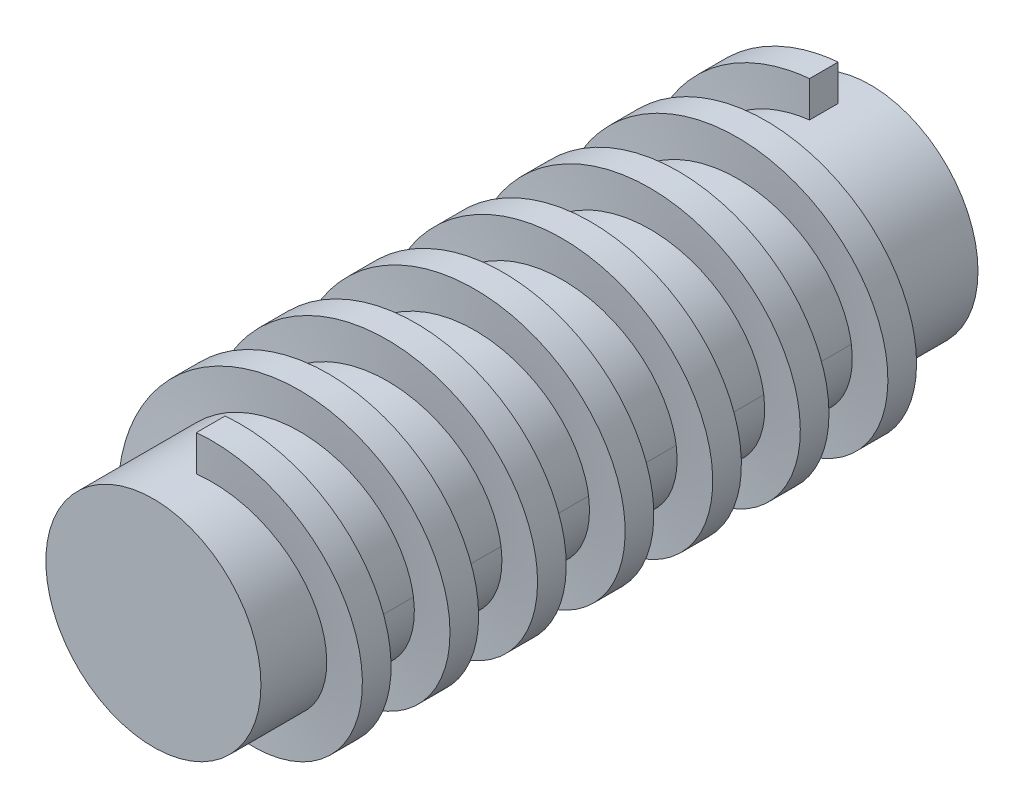
SolidWorks part; units mm, degrees
ref_plane "Front Plane" through (0, 0, 0) normal (0, 0, 1) x (1, 0, 0)
ref_plane "Top Plane" through (0, 0, 0) normal (0, 1, 0) x (1, 0, 0)
ref_plane "Right Plane" through (0, 0, 0) normal (1, 0, 0) x (0, 0, -1)
sketch "Sketch1" plane through (0, 0, 0) normal (0, 0, 1) x (1, 0, 0)
  circle A0 centre (0, 0) radius 15
  dimension "D1" = 30
extrude "Boss-Extrude1" add sketch "Sketch1" along normal mid plane 100
sketch "Sketch2" plane through (0, 0, 0) normal (1, 0, 0) x (0, 0, -1)
  line L0 (50, 15) -> (-50, 15) construction
  line L1 (-44, 15) -> (-40, 15)
  line L2 (-44, 15) -> (-44, 20)
  line L3 (-44, 20) -> (-40, 20)
  line L4 (-40, 15) -> (-40, 20)
  line L5 (-50, 15) -> (-50, -15) construction
  line L6 (-42, 20) -> (-42, 15)
  line L7 (0, 0) -> (0, 27.9327)
  line L8 (0, 0) -> (-50000, 0) construction
  dimension "D1" = 4
  dimension "D2" = 5
  dimension "D3" = 6
ref_plane "Plane1" through (0, 0, 44) normal (0, 0, 1) x (1, 0, 0)
sketch "Sketch4" plane through (0, 0, 44) normal (0, 0, 1) x (1, 0, 0)
  circle A0 centre (0, 0) radius 20
curve "Helix/Spiral1" pitch 12.2143 height 85.5 turns 7
ref_plane "Plane2" through (0, 0, 40) normal (0, 0, 1) x (1, 0, 0)
sketch "Sketch5" plane through (0, 0, 40) normal (0, 0, 1) x (1, 0, 0)
  circle A0 centre (0, 0) radius 20
curve "Helix/Spiral2" pitch 12.2143 height 85.5 turns 7
sketch "Sketch6" plane through (0, 0, 0) normal (1, 0, 0) x (0, 0, -1)
  line L0 (41.5, 20) -> (45.5, 20)
  line L1 (41.5, 20) -> (41.5, 15)
  line L2 (45.5, 20) -> (45.5, 15)
  line L3 (41.5, 15) -> (45.5, 15)
  spline S0 degree 3 poles (-44, 20) (-43.7943, 20) (-43.38, 19.3171) (-42.761, 16.347) (-42.1413, 11.7305) (-41.5217, 5.9325) (-40.9022, -0.463) (-40.2826, -6.8119) (-39.663, -12.4747) (-39.0435, -16.8811) (-38.4239, -19.5872) (-37.8043, -20.3204) (-37.1848, -19.0069) (-36.5652, -15.7791) (-35.9457, -10.962) (-35.3261, -5.0408) (-34.7065, 1.3882) (-34.087, 7.6773) (-33.4674, 13.1931) (-32.8478, 17.3801) (-32.2283, 19.8166) (-31.6087, 20.2572) (-30.9891, 18.6574) (-30.3696, 15.1785) (-29.75, 10.1707) (-29.1304, 4.1386) (-28.5109, -2.3104) (-27.8913, -8.5267) (-27.2717, -13.8841) (-26.6522, -17.8432) (-26.0326, -20.0051) (-25.413, -20.152) (-24.7935, -18.2692) (-24.1739, -14.5464) (-23.5543, -9.3584) (-22.9348, -3.2278) (-22.3152, 3.2278) (-21.6957, 9.3584) (-21.0761, 14.5464) (-20.4565, 18.2692) (-19.837, 20.152) (-19.2174, 20.0051) (-18.5978, 17.8432) (-17.9783, 13.8841) (-17.3587, 8.5267) (-16.7391, 2.3104) (-16.1196, -4.1386) (-15.5, -10.1707) (-14.8804, -15.1785) (-14.2609, -18.6574) (-13.6413, -20.2572) (-13.0217, -19.8166) (-12.4022, -17.3801) (-11.7826, -13.1931) (-11.163, -7.6773) (-10.5435, -1.3882) (-9.9239, 5.0408) (-9.3043, 10.962) (-8.6848, 15.7791) (-8.0652, 19.0069) (-7.4457, 20.3204) (-6.8261, 19.5872) (-6.2065, 16.8811) (-5.587, 12.4747) (-4.9674, 6.8119) (-4.3478, 0.463) (-3.7283, -5.9325) (-3.1087, -11.7305) (-2.4891, -16.347) (-1.8696, -19.3171) (-1.25, -20.3415) (-0.6304, -19.3171) (-0.0109, -16.347) (0.6087, -11.7305) (1.2283, -5.9325) (1.8478, 0.463) (2.4674, 6.8119) (3.087, 12.4747) (3.7065, 16.8811) (4.3261, 19.5872) (4.9457, 20.3204) (5.5652, 19.0069) (6.1848, 15.7791) (6.8043, 10.962) (7.4239, 5.0408) (8.0435, -1.3882) (8.663, -7.6773) (9.2826, -13.1931) (9.9022, -17.3801) (10.5217, -19.8166) (11.1413, -20.2572) (11.7609, -18.6574) (12.3804, -15.1785) (13, -10.1707) (13.6196, -4.1386) (14.2391, 2.3104) (14.8587, 8.5267) (15.4783, 13.8841) (16.0978, 17.8432) (16.7174, 20.0051) (17.337, 20.152) (17.9565, 18.2692) (18.5761, 14.5464) (19.1957, 9.3584) (19.8152, 3.2278) (20.4348, -3.2278) (21.0543, -9.3584) (21.6739, -14.5464) (22.2935, -18.2692) (22.913, -20.152) (23.5326, -20.0051) (24.1522, -17.8432) (24.7717, -13.8841) (25.3913, -8.5267) (26.0109, -2.3104) (26.6304, 4.1386) (27.25, 10.1707) (27.8696, 15.1785) (28.4891, 18.6574) (29.1087, 20.2572) (29.7283, 19.8166) (30.3478, 17.3801) (30.9674, 13.1931) (31.587, 7.6773) (32.2065, 1.3882) (32.8261, -5.0408) (33.4457, -10.962) (34.0652, -15.7791) (34.6848, -19.0069) (35.3043, -20.3204) (35.9239, -19.5872) (36.5435, -16.8811) (37.163, -12.4747) (37.7826, -6.8119) (38.4022, -0.463) (39.0217, 5.9325) (39.6413, 11.7305) (40.261, 16.347) (40.88, 19.3171) (41.2943, 20) (41.5, 20) knots 0 0 0 0 0.007246 0.014493 0.021739 0.028986 0.036232 0.043478 0.050725 0.057971 0.065217 0.072464 0.07971 0.086957 0.094203 0.101449 0.108696 0.115942 0.123188 0.130435 0.137681 0.144928 0.152174 0.15942 0.166667 0.173913 0.181159 0.188406 0.195652 0.202899 0.210145 0.217391 0.224638 0.231884 0.23913 0.246377 0.253623 0.26087 0.268116 0.275362 0.282609 0.289855 0.297101 0.304348 0.311594 0.318841 0.326087 0.333333 0.34058 0.347826 0.355072 0.362319 0.369565 0.376812 0.384058 0.391304 0.398551 0.405797 0.413043 0.42029 0.427536 0.434783 0.442029 0.449275 0.456522 0.463768 0.471014 0.478261 0.485507 0.492754 0.5 0.507246 0.514493 0.521739 0.528986 0.536232 0.543478 0.550725 0.557971 0.565217 0.572464 0.57971 0.586957 0.594203 0.601449 0.608696 0.615942 0.623188 0.630435 0.637681 0.644928 0.652174 0.65942 0.666667 0.673913 0.681159 0.688406 0.695652 0.702899 0.710145 0.717391 0.724638 0.731884 0.73913 0.746377 0.753623 0.76087 0.768116 0.775362 0.782609 0.789855 0.797101 0.804348 0.811594 0.818841 0.826087 0.833333 0.84058 0.847826 0.855072 0.862319 0.869565 0.876812 0.884058 0.891304 0.898551 0.905797 0.913043 0.92029 0.927536 0.934783 0.942029 0.949275 0.956522 0.963768 0.971014 0.978261 0.985507 0.992754 1 1 1 1 construction
  spline S1 degree 3 poles (-40, 20) (-39.7943, 20) (-39.38, 19.3171) (-38.761, 16.347) (-38.1413, 11.7305) (-37.5217, 5.9325) (-36.9022, -0.463) (-36.2826, -6.8119) (-35.663, -12.4747) (-35.0435, -16.8811) (-34.4239, -19.5872) (-33.8043, -20.3204) (-33.1848, -19.0069) (-32.5652, -15.7791) (-31.9457, -10.962) (-31.3261, -5.0408) (-30.7065, 1.3882) (-30.087, 7.6773) (-29.4674, 13.1931) (-28.8478, 17.3801) (-28.2283, 19.8166) (-27.6087, 20.2572) (-26.9891, 18.6574) (-26.3696, 15.1785) (-25.75, 10.1707) (-25.1304, 4.1386) (-24.5109, -2.3104) (-23.8913, -8.5267) (-23.2717, -13.8841) (-22.6522, -17.8432) (-22.0326, -20.0051) (-21.413, -20.152) (-20.7935, -18.2692) (-20.1739, -14.5464) (-19.5543, -9.3584) (-18.9348, -3.2278) (-18.3152, 3.2278) (-17.6957, 9.3584) (-17.0761, 14.5464) (-16.4565, 18.2692) (-15.837, 20.152) (-15.2174, 20.0051) (-14.5978, 17.8432) (-13.9783, 13.8841) (-13.3587, 8.5267) (-12.7391, 2.3104) (-12.1196, -4.1386) (-11.5, -10.1707) (-10.8804, -15.1785) (-10.2609, -18.6574) (-9.6413, -20.2572) (-9.0217, -19.8166) (-8.4022, -17.3801) (-7.7826, -13.1931) (-7.163, -7.6773) (-6.5435, -1.3882) (-5.9239, 5.0408) (-5.3043, 10.962) (-4.6848, 15.7791) (-4.0652, 19.0069) (-3.4457, 20.3204) (-2.8261, 19.5872) (-2.2065, 16.8811) (-1.587, 12.4747) (-0.9674, 6.8119) (-0.3478, 0.463) (0.2717, -5.9325) (0.8913, -11.7305) (1.5109, -16.347) (2.1304, -19.3171) (2.75, -20.3415) (3.3696, -19.3171) (3.9891, -16.347) (4.6087, -11.7305) (5.2283, -5.9325) (5.8478, 0.463) (6.4674, 6.8119) (7.087, 12.4747) (7.7065, 16.8811) (8.3261, 19.5872) (8.9457, 20.3204) (9.5652, 19.0069) (10.1848, 15.7791) (10.8043, 10.962) (11.4239, 5.0408) (12.0435, -1.3882) (12.663, -7.6773) (13.2826, -13.1931) (13.9022, -17.3801) (14.5217, -19.8166) (15.1413, -20.2572) (15.7609, -18.6574) (16.3804, -15.1785) (17, -10.1707) (17.6196, -4.1386) (18.2391, 2.3104) (18.8587, 8.5267) (19.4783, 13.8841) (20.0978, 17.8432) (20.7174, 20.0051) (21.337, 20.152) (21.9565, 18.2692) (22.5761, 14.5464) (23.1957, 9.3584) (23.8152, 3.2278) (24.4348, -3.2278) (25.0543, -9.3584) (25.6739, -14.5464) (26.2935, -18.2692) (26.913, -20.152) (27.5326, -20.0051) (28.1522, -17.8432) (28.7717, -13.8841) (29.3913, -8.5267) (30.0109, -2.3104) (30.6304, 4.1386) (31.25, 10.1707) (31.8696, 15.1785) (32.4891, 18.6574) (33.1087, 20.2572) (33.7283, 19.8166) (34.3478, 17.3801) (34.9674, 13.1931) (35.587, 7.6773) (36.2065, 1.3882) (36.8261, -5.0408) (37.4457, -10.962) (38.0652, -15.7791) (38.6848, -19.0069) (39.3043, -20.3204) (39.9239, -19.5872) (40.5435, -16.8811) (41.163, -12.4747) (41.7826, -6.8119) (42.4022, -0.463) (43.0217, 5.9325) (43.6413, 11.7305) (44.261, 16.347) (44.88, 19.3171) (45.2943, 20) (45.5, 20) knots 0 0 0 0 0.007246 0.014493 0.021739 0.028986 0.036232 0.043478 0.050725 0.057971 0.065217 0.072464 0.07971 0.086957 0.094203 0.101449 0.108696 0.115942 0.123188 0.130435 0.137681 0.144928 0.152174 0.15942 0.166667 0.173913 0.181159 0.188406 0.195652 0.202899 0.210145 0.217391 0.224638 0.231884 0.23913 0.246377 0.253623 0.26087 0.268116 0.275362 0.282609 0.289855 0.297101 0.304348 0.311594 0.318841 0.326087 0.333333 0.34058 0.347826 0.355072 0.362319 0.369565 0.376812 0.384058 0.391304 0.398551 0.405797 0.413043 0.42029 0.427536 0.434783 0.442029 0.449275 0.456522 0.463768 0.471014 0.478261 0.485507 0.492754 0.5 0.507246 0.514493 0.521739 0.528986 0.536232 0.543478 0.550725 0.557971 0.565217 0.572464 0.57971 0.586957 0.594203 0.601449 0.608696 0.615942 0.623188 0.630435 0.637681 0.644928 0.652174 0.65942 0.666667 0.673913 0.681159 0.688406 0.695652 0.702899 0.710145 0.717391 0.724638 0.731884 0.73913 0.746377 0.753623 0.76087 0.768116 0.775362 0.782609 0.789855 0.797101 0.804348 0.811594 0.818841 0.826087 0.833333 0.84058 0.847826 0.855072 0.862319 0.869565 0.876812 0.884058 0.891304 0.898551 0.905797 0.913043 0.92029 0.927536 0.934783 0.942029 0.949275 0.956522 0.963768 0.971014 0.978261 0.985507 0.992754 1 1 1 1 construction
  dimension "D1" = 5
sketch "Sketch7" plane through (0, 0, 50) normal (0, 0, 1) x (1, 0, 0)
  circle A0 centre (0, 0) radius 17.5
  dimension "D1" = 35
ref_plane "Plane3" through (0, 0, 42) normal (0, 0, 1) x (1, 0, 0)
sketch "Sketch8" plane through (0, 0, 42) normal (0, 0, 1) x (1, 0, 0)
  circle A0 centre (0, 0) radius 17.5
  dimension "D1" = 35
curve "Helix/Spiral3" pitch 12.2143 height 85.5 radius 17.5 centre (0, 0, 42) axis (0, 0, -1) start towards (0, 1, 0)
sweep "Sweep1" add profiles "Sketch2" path "Helix/Spiral3"
